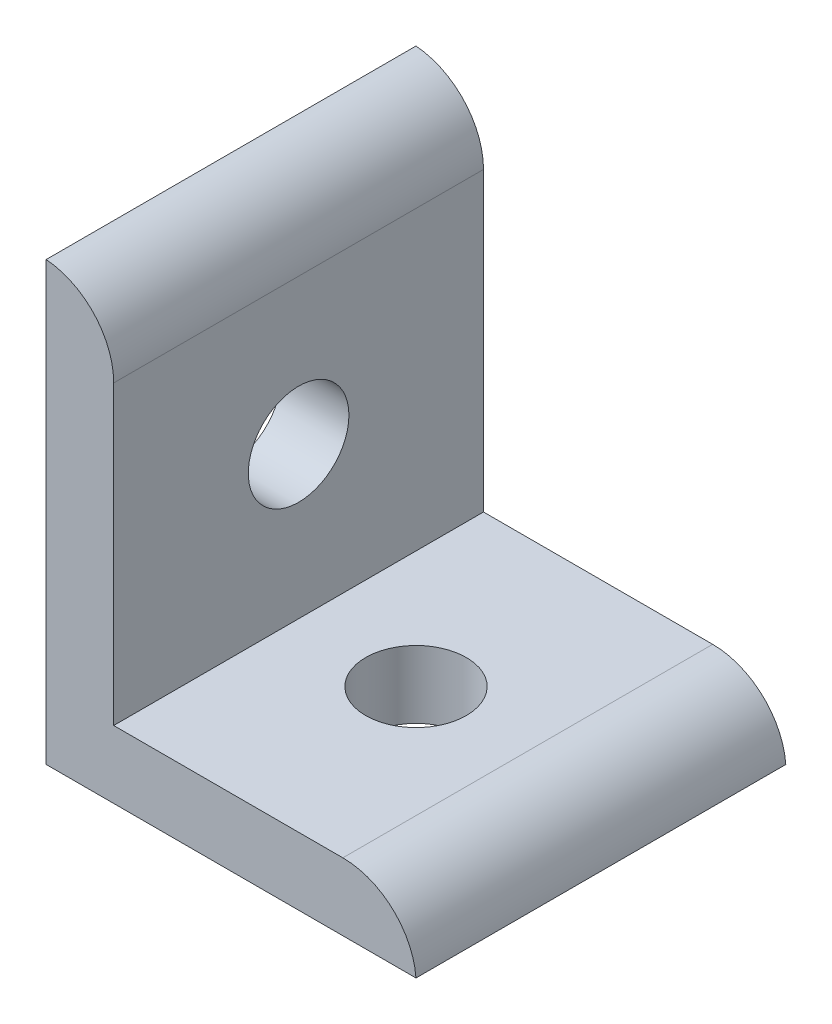
SolidWorks part; units mm, degrees
ref_plane "Front Plane" through (0, 0, 0) normal (0, 0, 1) x (1, 0, 0)
ref_plane "Top Plane" through (0, 0, 0) normal (0, 1, 0) x (1, 0, 0)
ref_plane "Right Plane" through (0, 0, 0) normal (1, 0, 0) x (0, 0, -1)
sketch "Sketch1" plane through (0, 0, 0) normal (0, 1, 0) x (1, 0, 0)
  line L1 (0, 0) -> (25.2, 0)
  line L2 (0, 0) -> (0, 25.2)
  line L3 (0, 25.2) -> (25.2, 25.2)
  line L4 (25.2, 0) -> (25.2, 25.2)
  circle A0 centre (12.6, 12.6) radius 3.429
  point P7 (0, 12.6)
  point P8 (12.6, 25.2)
  dimension "D2" = 6.858
  dimension "D1" = 25.2
extrude "Boss-Extrude1" add sketch "Sketch1" along normal blind 4.6
sketch "Sketch2" plane through (0, 4.6, 0) normal (0, 1, 0) x (1, 0, 0)
  line L0 (0, 0) -> (25.2, 0) construction
  line L1 (0, 25.2) -> (4.6, 25.2)
  line L2 (0, 25.2) -> (0, 0)
  line L3 (0, 0) -> (4.6, 0)
  line L4 (4.6, 25.2) -> (4.6, 0)
  dimension "D1" = 4.6
extrude "Boss-Extrude2" add sketch "Sketch2" along normal blind 25.2
sketch "Sketch3" plane through (4.6, 0, 0) normal (1, 0, 0) x (0, 0, -1)
  line L0 (0, 29.8) -> (25.2, 0) construction
  circle A0 centre (12.6, 14.9) radius 3.429
  point P6 (12.6, 14.9)
  dimension "D1" = 6.858
extrude "Cut-Extrude1" cut sketch "Sketch3" against normal up to next
fillet "Fillet1" radius 5 2 edges at (4.6, 29.8, -12.6) (25.2, 4.6, -12.6)
